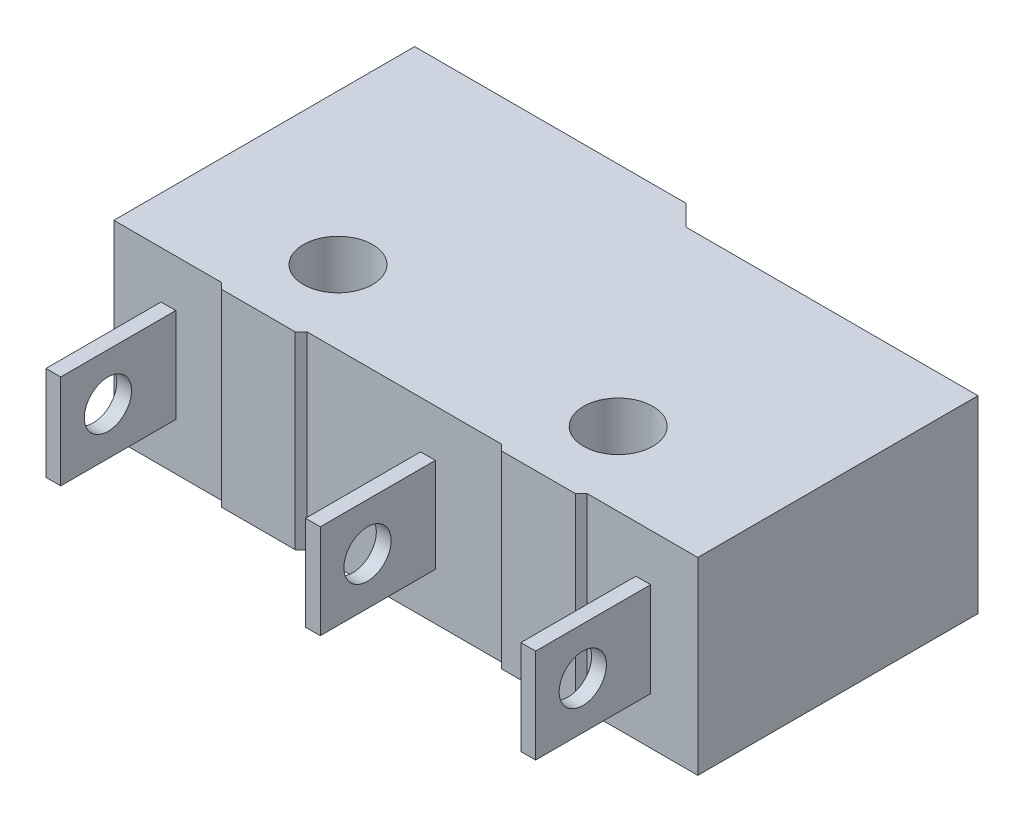
SolidWorks part; units mm, degrees
ref_plane "Front Plane" through (0, 0, 0) normal (0, 0, 1) x (1, 0, 0)
ref_plane "Top Plane" through (0, 0, 0) normal (0, 1, 0) x (1, 0, 0)
ref_plane "Right Plane" through (0, 0, 0) normal (1, 0, 0) x (0, 0, -1)
sketch "Sketch1" plane through (0, 0, 0) normal (0, 1, 0) x (1, 0, 0)
  line L0 (0, 0) -> (-9.5, 0) construction
  line L1 (-14.6, -2.5) -> (5.2, -2.5) construction
  line L2 (5.2, -2.5) -> (5.2, 7.7) construction
  line L3 (5.2, 7.7) -> (-14.6, 7.7) construction
  line L4 (-14.6, 7.7) -> (-14.6, -2.5) construction
  line L5 (-14.6, 7) -> (5.2, 7) construction
  line L6 (-9.5, 0) -> (-9.5, -2.5) construction
  line L7 (0, 0) -> (0, -2.5) construction
  line L8 (-13, -2.5) -> (-13, -6.4) construction
  line L9 (-13, -6.4) -> (3.6, -6.4) construction
  line L10 (3.6, -6.4) -> (3.6, -2.5) construction
  line L11 (3.1, -2.5) -> (3.1, -6.4) construction
  line L12 (-12.5, -2.5) -> (-12.5, -6.4) construction
  line L13 (-4.2, -2.5) -> (-4.2, -6.4) construction
  line L14 (-3.7, -2.5) -> (-3.7, -6.4) construction
  line L15 (-13, -4.45) -> (-12.5, -4.45) construction
  line L16 (-4.2, -4.45) -> (-3.7, -4.45) construction
  line L17 (3.1, -4.45) -> (3.6, -4.45) construction
  line L18 (-8.5, 7) -> (-8.5, 8.9) construction
  line L19 (-8.5, 8.9) -> (-6.5, 8.9) construction
  line L20 (-6.5, 8.9) -> (-6.5, 7) construction
  line L21 (-7.5, 8.9) -> (-7.5, 7) construction
  line L22 (-8.5, 8.4) -> (-6.5, 8.4) construction
  line L23 (-5.4, 7.7) -> (-4.7, 7) construction
  line L24 (-5.4, 7.7) -> (-5.4, 7) construction
  line L25 (-5.4, 7) -> (-4.7, 7) construction
  line L26 (-10.95, -2.5) -> (-10.75, -2.7)
  line L27 (-10.75, -2.7) -> (-8.25, -2.7)
  line L28 (-8.25, -2.7) -> (-8.05, -2.5)
  line L29 (-10.95, -2.5) -> (-10.95, -2.7) construction
  line L30 (-10.95, -2.7) -> (-10.75, -2.7) construction
  line L31 (-1.45, -2.5) -> (-1.25, -2.7)
  line L32 (-1.25, -2.7) -> (1.25, -2.7)
  line L33 (1.25, -2.7) -> (1.45, -2.5)
  line L34 (-8.05, -2.5) -> (-1.45, -2.5)
  line L35 (1.45, -2.5) -> (5.2, -2.5)
  line L36 (5.2, -2.5) -> (5.2, 7)
  line L37 (5.2, 7) -> (-4.7, 7)
  line L38 (-4.7, 7) -> (-5.4, 7.7)
  line L39 (-5.4, 7.7) -> (-14.6, 7.7)
  line L40 (-14.6, 7.7) -> (-14.6, -2.5)
  line L41 (-14.6, -2.5) -> (-10.95, -2.5)
  circle A0 centre (0, 0) radius 1.175
  circle A1 centre (-9.5, 0) radius 1.175
  dimension "D1" = 2.35
  dimension "D2" = 9.5
  dimension "D3" = 2.5
  dimension "D4" = 9.5
  dimension "D5" = 10.2
  dimension "D6" = 5.1
  dimension "D7" = 19.8
  dimension "D8" = 0.5
  dimension "D9" = 1.6
  dimension "D10" = 8.8
  dimension "D11" = 7.3
  dimension "D12" = 6.4
  dimension "D13" = 2
  dimension "D14" = 7.5
  dimension "D15" = 0.5
  dimension "D16" = 8.4
  dimension "D17" = 2.5
  dimension "D18" = 0.4
sketch "Sketch2" plane through (0, 0, 0) normal (1, 0, 0) x (0, 0, -1)
  line L0 (-2.5, 0) -> (7.7, 0) construction
  line L1 (7.7, 0) -> (7.7, 6.4) construction
  line L2 (7.7, 6.4) -> (-2.5, 6.4) construction
  line L3 (-2.5, 6.4) -> (-2.5, 0) construction
  line L4 (-2.5, 3.2) -> (7.7, 3.2) construction
  line L5 (7.7, 4.8) -> (8.9, 4.8) construction
  line L6 (8.9, 4.8) -> (8.9, 1.6) construction
  line L7 (8.9, 1.6) -> (7.7, 1.6) construction
  line L8 (-2.5, 4.8) -> (-6.4, 4.8) construction
  line L9 (-6.4, 4.8) -> (-6.4, 1.6) construction
  line L10 (-6.4, 1.6) -> (-2.5, 1.6) construction
  dimension "D1" = 6.4
  dimension "D2" = 3.2
extrude "Boss-Extrude1" add sketch "Sketch1" along normal up to vertex (6.4 mm away) up to point (0, 6.4, -7.7)
ref_plane "Plane1" through (0, 1.6, 0) normal (0, 1, 0) x (1, 0, 0)
sketch "Sketch3" plane through (0, 1.6, 0) normal (0, 1, 0) x (1, 0, 0)
  line L0 (-7.5, 8.9) -> (-7.5, 7) construction
  line L1 (-8.5, 7) -> (-8.5, 8.9) construction
  line L2 (-6.5, 8.9) -> (-6.5, 7) construction
  line L3 (-8.5, 8.9) -> (-6.5, 8.9) construction
  line L4 (-7.5, 8.9) -> (-7.5, 7) construction
  line L5 (-8.5, 7) -> (-8.5, 8.9) construction
  line L6 (-6.5, 8.9) -> (-6.5, 7) construction
  line L7 (-8.5, 8.9) -> (-6.5, 8.9) construction
  line L8 (-8.5, 7) -> (-6.5, 7)
  line L9 (-8.5, 7.9) -> (-8.5, 7)
  line L10 (-6.5, 7.9) -> (-6.5, 7)
  arc A0 (-6.5, 7.9) -> (-8.5, 7.9) centre (-7.5, 7.9) ccw
extrude "Boss-Extrude2" add sketch "Sketch3" along normal up to vertex (3.2 mm away) up to point (0, 4.8, -8.9)
sketch "Sketch4" plane through (0, 1.6, 0) normal (0, 1, 0) x (1, 0, 0)
  line L0 (-12.5, -2.5) -> (-12.5, -6.4) construction
  line L1 (-13, -2.5) -> (-13, -6.4) construction
  line L2 (-4.2, -2.5) -> (-4.2, -6.4) construction
  line L3 (-3.7, -2.5) -> (-3.7, -6.4) construction
  line L4 (3.6, -6.4) -> (3.6, -2.5) construction
  line L5 (3.1, -2.5) -> (3.1, -6.4) construction
  line L6 (-13, -6.4) -> (3.6, -6.4) construction
  line L7 (-12.5, -2.5) -> (-12.5, -6.4)
  line L8 (-13, -2.5) -> (-13, -6.4)
  line L9 (-4.2, -2.5) -> (-4.2, -6.4)
  line L10 (-3.7, -2.5) -> (-3.7, -6.4)
  line L11 (3.6, -6.4) -> (3.6, -2.5)
  line L12 (3.1, -2.5) -> (3.1, -6.4)
  line L13 (-13, -6.4) -> (3.6, -6.4) construction
  line L14 (-13, -6.4) -> (-12.5, -6.4)
  line L15 (-4.2, -6.4) -> (-3.7, -6.4)
  line L16 (3.1, -6.4) -> (3.6, -6.4)
  line L17 (3.6, -2.5) -> (3.1, -2.5)
  line L18 (-3.7, -2.5) -> (-4.2, -2.5)
  line L19 (-12.5, -2.5) -> (-13, -2.5)
extrude "Boss-Extrude3" add sketch "Sketch4" along normal up to vertex (3.2 mm away) up to point (0, 4.8, 6.4)
sketch "Sketch5" plane through (3.6, 0, 0) normal (1, 0, 0) x (0, 0, -1)
  line L0 (-6.4, 3.2) -> (-4.8, 3.2) construction
  line L1 (-6.4, 4.8) -> (-6.4, 1.6) construction
  line L2 (-4.8, 3.2) -> (-4.8, 1.6) construction
  line L3 (-6.4, 1.6) -> (-2.5, 1.6) construction
  line L4 (-4.8, 3.2) -> (-4.8, 4.8) construction
  line L5 (-6.4, 4.8) -> (-2.5, 4.8) construction
  circle A0 centre (-4.8, 3.2) radius 0.8
  dimension "D1" = 1.6
extrude "Cut-Extrude1" cut sketch "Sketch5" against normal through all
